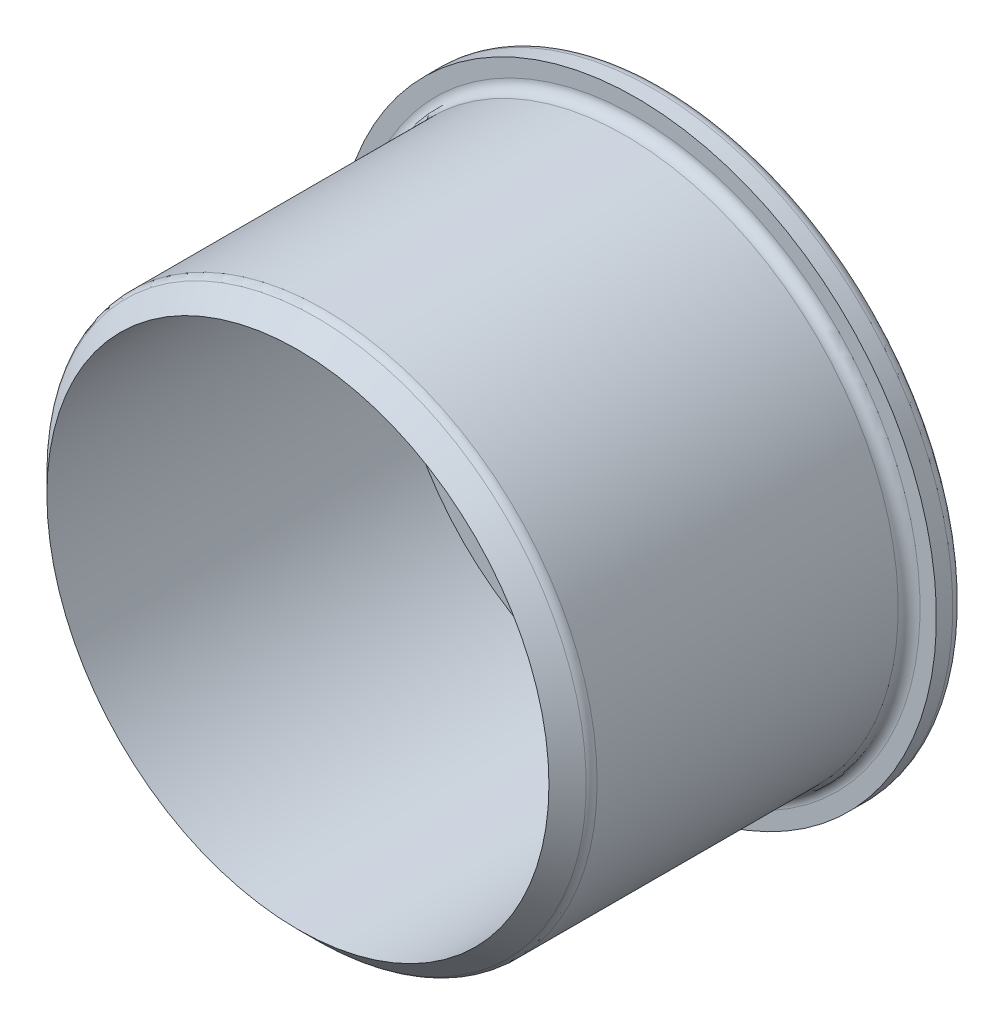
SolidWorks part; units mm, degrees
ref_plane "Спереди" through (0, 0, 0) normal (0, 0, 1) x (1, 0, 0)
ref_plane "Сверху" through (0, 0, 0) normal (0, 1, 0) x (1, 0, 0)
ref_plane "Справа" through (0, 0, 0) normal (1, 0, 0) x (0, 0, -1)
sketch "Эскиз1" plane through (0, 0, 0) normal (0, 0, 1) x (1, 0, 0)
  circle A0 centre (0, 0) radius 25
  dimension "D1" = 50
extrude "Бобышка-Вытянуть1" add sketch "Эскиз1" along normal blind 32 contours A0
sketch "Эскиз2" plane through (0, 0, 0) normal (0, 0, -1) x (-1, 0, 0)
  circle A0 centre (0, 0) radius 27.5
  dimension "D1" = 55
extrude "Бобышка-Вытянуть2" add sketch "Эскиз2" along normal blind 2.5
sketch "Эскиз3" plane through (0, 0, 32) normal (0, 0, 1) x (1, 0, 0)
  circle A0 centre (0, 0) radius 23
  dimension "D1" = 46
extrude "Вырез-Вытянуть1" cut sketch "Эскиз3" against normal blind 32.5
chamfer "Фаска1" distance 3 angle 45 1 edges at (25, 0, 32)
fillet "Скругление1" radius 1 1 edges at (25, 0, 29)
fillet "Скругление2" radius 1 1 edges at (25, 0, 0)
fillet "Скругление3" radius 1 1 edges at (-27.5, 0, -2.5)
sketch "Эскиз4" plane through (0, 0, -2.5) normal (0, 0, -1) x (-1, 0, 0)
  circle A0 centre (0, 0) radius 1.6
  dimension "D1" = 3.2
extrude "Вырез-Вытянуть2" cut sketch "Эскиз4" against normal blind 32.5
sketch "Эскиз5" plane through (0, 0, -2.5) normal (0, 0, -1) x (-1, 0, 0)
  circle A0 centre (0, 0) radius 7
  dimension "D1" = 14
extrude "Вырез-Вытянуть3" cut sketch "Эскиз5" against normal blind 10
